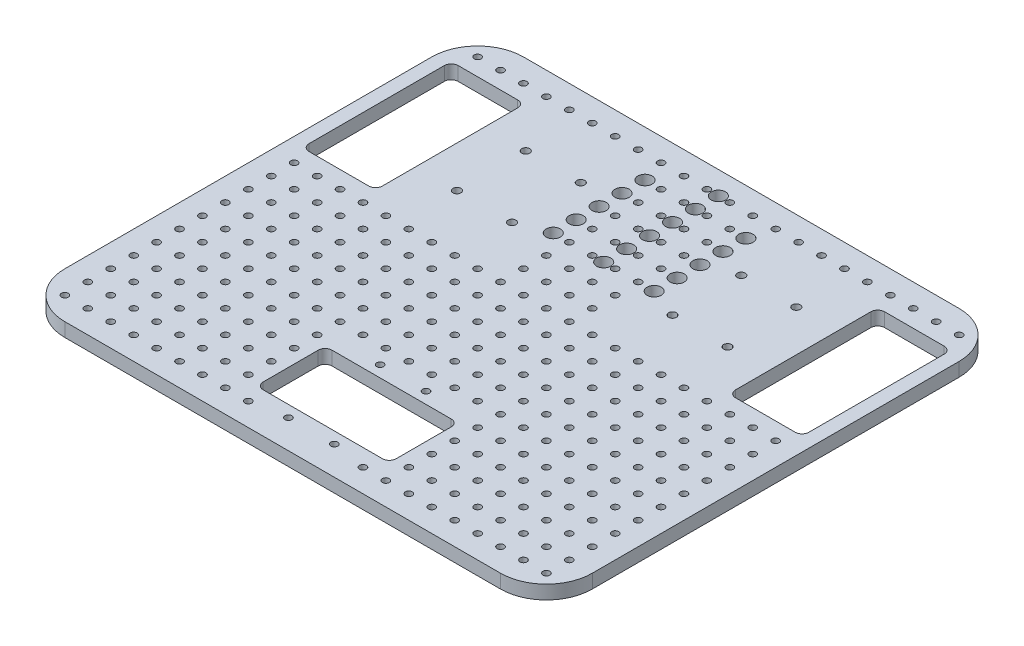
SolidWorks part; units mm, degrees
ref_plane "Спереди" through (0, 0, 0) normal (0, 0, 1) x (1, 0, 0)
ref_plane "Сверху" through (0, 0, 0) normal (0, 1, 0) x (1, 0, 0)
ref_plane "Справа" through (0, 0, 0) normal (1, 0, 0) x (0, 0, -1)
sketch "Эскиз1" plane through (0, 0, 0) normal (0, 1, 0) x (1, 0, 0)
  line L0 (94.4, 150) -> (0, 150) construction
  line L1 (0, 0) -> (230, 0)
  line L6 (115, 0) -> (115, 118.2603) construction
  line L10 (230, 0) -> (230, 200)
  line L28 (230, 200) -> (0, 200)
  line L29 (0, 200) -> (0, 0)
  circle A16 centre (80, 135) radius 1.73
  circle A19 centre (80, 165) radius 1.73
  circle A22 centre (56, 165) radius 1.73
  circle A23 centre (56, 135) radius 1.73
  circle A24 centre (150, 135) radius 1.73
  circle A25 centre (174, 135) radius 1.73
  circle A26 centre (150, 165) radius 1.73
  circle A27 centre (174, 165) radius 1.73
  point P7 (115, 25)
  dimension "D1" = 230
  dimension "D2" = 200
  dimension "D3" = 150
  dimension "D7" = 24
  dimension "D8" = 30
  dimension "D9" = 35
extrude "Бобышка-Вытянуть1" add sketch "Эскиз1" along normal blind 6
fillet "Скругление1" radius 20 4 edges at (0, 3, 0) (230, 3, 0) (230, 3, -200) (0, 3, -200)
sketch "Эскиз2" plane through (0, 6, 0) normal (0, 1, 0) x (1, 0, 0)
  line L0 (174, 165) -> (174, 135) construction
  line L1 (224, 182.5) -> (192, 182.5)
  line L2 (224, 182.5) -> (224, 117.5)
  line L3 (224, 117.5) -> (192, 117.5)
  line L4 (192, 182.5) -> (192, 117.5)
  line L5 (174, 150) -> (192, 150) construction
  line L6 (115, 200) -> (115, 0) construction
  line L7 (210, 200) -> (20, 200) construction
  line L8 (20, 0) -> (210, 0) construction
  line L9 (56, 150) -> (38, 150) construction
  line L10 (56, 165) -> (56, 135) construction
  line L11 (38, 182.5) -> (38, 117.5)
  line L12 (6, 117.5) -> (38, 117.5)
  line L13 (6, 182.5) -> (6, 117.5)
  line L14 (6, 182.5) -> (38, 182.5)
  line L15 (86, 32.5) -> (144, 32.5) construction
  line L16 (86, 47.5) -> (144, 47.5)
  line L17 (86, 47.5) -> (86, 17.5)
  line L18 (86, 17.5) -> (144, 17.5)
  line L19 (144, 47.5) -> (144, 17.5)
  circle A0 centre (105, 12.5) radius 1.5
  circle A1 centre (125, 12.5) radius 1.5
  circle A2 centre (105, 52.5) radius 1.5
  circle A3 centre (125, 52.5) radius 1.5
  dimension "D7" = 3
  dimension "D1" = 65
  dimension "D2" = 18
  dimension "D3" = 32
  dimension "D4" = 58
  dimension "D5" = 30
  dimension "D6" = 17.5
  dimension "D8" = 20
  dimension "D9" = 40
extrude "Вырез-Вытянуть1" cut sketch "Эскиз2" against normal blind 10
fillet "Скругление2" radius 3 12 edges at (224, 3, -117.5) (224, 3, -182.5) (192, 3, -182.5) (192, 3, -117.5) (6, 3, -117.5) (38, 3, -117.5) (38, 3, -182.5) (6, 3, -182.5) (86, 3, -17.5) (144, 3, -17.5) (144, 3, -47.5) (86, 3, -47.5)
sketch "Эскиз3" plane through (0, 6, 0) normal (0, 1, 0) x (1, 0, 0)
  line L0 (20, 0) -> (210, 0) construction
  line L1 (0, 180) -> (0, 20) construction
  line L2 (115, 190) -> (115, 200) construction
  line L3 (210, 200) -> (20, 200) construction
  circle A0 centre (10, 10) radius 1.5
  circle A1 centre (20, 10) radius 1.5
  circle A2 centre (30, 10) radius 1.5
  circle A3 centre (40, 10) radius 1.5
  circle A4 centre (50, 10) radius 1.5
  circle A5 centre (60, 10) radius 1.5
  circle A6 centre (70, 10) radius 1.5
  circle A7 centre (80, 10) radius 1.5
  circle A8 centre (90, 10) radius 1.5
  circle A13 centre (140, 10) radius 1.5
  circle A14 centre (150, 10) radius 1.5
  circle A15 centre (160, 10) radius 1.5
  circle A16 centre (170, 10) radius 1.5
  circle A17 centre (180, 10) radius 1.5
  circle A18 centre (190, 10) radius 1.5
  circle A19 centre (200, 10) radius 1.5
  circle A20 centre (210, 10) radius 1.5
  circle A21 centre (220, 10) radius 1.5
  circle A22 centre (20, 20) radius 1.5
  circle A23 centre (30, 20) radius 1.5
  circle A24 centre (40, 20) radius 1.5
  circle A25 centre (50, 20) radius 1.5
  circle A26 centre (60, 20) radius 1.5
  circle A27 centre (70, 20) radius 1.5
  circle A28 centre (80, 20) radius 1.5
  circle A35 centre (150, 20) radius 1.5
  circle A36 centre (160, 20) radius 1.5
  circle A37 centre (170, 20) radius 1.5
  circle A38 centre (180, 20) radius 1.5
  circle A39 centre (190, 20) radius 1.5
  circle A40 centre (200, 20) radius 1.5
  circle A41 centre (210, 20) radius 1.5
  circle A42 centre (220, 20) radius 1.5
  circle A43 centre (20, 30) radius 1.5
  circle A44 centre (30, 30) radius 1.5
  circle A45 centre (40, 30) radius 1.5
  circle A46 centre (50, 30) radius 1.5
  circle A47 centre (60, 30) radius 1.5
  circle A48 centre (70, 30) radius 1.5
  circle A49 centre (80, 30) radius 1.5
  circle A56 centre (150, 30) radius 1.5
  circle A57 centre (160, 30) radius 1.5
  circle A58 centre (170, 30) radius 1.5
  circle A59 centre (180, 30) radius 1.5
  circle A60 centre (190, 30) radius 1.5
  circle A61 centre (200, 30) radius 1.5
  circle A62 centre (210, 30) radius 1.5
  circle A63 centre (220, 30) radius 1.5
  circle A64 centre (20, 40) radius 1.5
  circle A65 centre (30, 40) radius 1.5
  circle A66 centre (40, 40) radius 1.5
  circle A67 centre (50, 40) radius 1.5
  circle A68 centre (60, 40) radius 1.5
  circle A69 centre (70, 40) radius 1.5
  circle A70 centre (80, 40) radius 1.5
  circle A77 centre (150, 40) radius 1.5
  circle A78 centre (160, 40) radius 1.5
  circle A79 centre (170, 40) radius 1.5
  circle A80 centre (180, 40) radius 1.5
  circle A81 centre (190, 40) radius 1.5
  circle A82 centre (200, 40) radius 1.5
  circle A83 centre (210, 40) radius 1.5
  circle A84 centre (220, 40) radius 1.5
  circle A85 centre (20, 50) radius 1.5
  circle A86 centre (30, 50) radius 1.5
  circle A87 centre (40, 50) radius 1.5
  circle A88 centre (50, 50) radius 1.5
  circle A89 centre (60, 50) radius 1.5
  circle A90 centre (70, 50) radius 1.5
  circle A91 centre (80, 50) radius 1.5
  circle A98 centre (150, 50) radius 1.5
  circle A99 centre (160, 50) radius 1.5
  circle A100 centre (170, 50) radius 1.5
  circle A101 centre (180, 50) radius 1.5
  circle A102 centre (190, 50) radius 1.5
  circle A103 centre (200, 50) radius 1.5
  circle A104 centre (210, 50) radius 1.5
  circle A105 centre (220, 50) radius 1.5
  circle A106 centre (20, 60) radius 1.5
  circle A107 centre (30, 60) radius 1.5
  circle A108 centre (40, 60) radius 1.5
  circle A109 centre (50, 60) radius 1.5
  circle A110 centre (60, 60) radius 1.5
  circle A111 centre (70, 60) radius 1.5
  circle A112 centre (80, 60) radius 1.5
  circle A113 centre (90, 60) radius 1.5
  circle A114 centre (100, 60) radius 1.5
  circle A115 centre (110, 60) radius 1.5
  circle A116 centre (120, 60) radius 1.5
  circle A117 centre (130, 60) radius 1.5
  circle A118 centre (140, 60) radius 1.5
  circle A119 centre (150, 60) radius 1.5
  circle A120 centre (160, 60) radius 1.5
  circle A121 centre (170, 60) radius 1.5
  circle A122 centre (180, 60) radius 1.5
  circle A123 centre (190, 60) radius 1.5
  circle A124 centre (200, 60) radius 1.5
  circle A125 centre (210, 60) radius 1.5
  circle A126 centre (220, 60) radius 1.5
  circle A127 centre (20, 70) radius 1.5
  circle A128 centre (30, 70) radius 1.5
  circle A129 centre (40, 70) radius 1.5
  circle A130 centre (50, 70) radius 1.5
  circle A131 centre (60, 70) radius 1.5
  circle A132 centre (70, 70) radius 1.5
  circle A133 centre (80, 70) radius 1.5
  circle A134 centre (90, 70) radius 1.5
  circle A135 centre (100, 70) radius 1.5
  circle A136 centre (110, 70) radius 1.5
  circle A137 centre (120, 70) radius 1.5
  circle A138 centre (130, 70) radius 1.5
  circle A139 centre (140, 70) radius 1.5
  circle A140 centre (150, 70) radius 1.5
  circle A141 centre (160, 70) radius 1.5
  circle A142 centre (170, 70) radius 1.5
  circle A143 centre (180, 70) radius 1.5
  circle A144 centre (190, 70) radius 1.5
  circle A145 centre (200, 70) radius 1.5
  circle A146 centre (210, 70) radius 1.5
  circle A147 centre (220, 70) radius 1.5
  circle A148 centre (20, 80) radius 1.5
  circle A149 centre (30, 80) radius 1.5
  circle A150 centre (40, 80) radius 1.5
  circle A151 centre (50, 80) radius 1.5
  circle A152 centre (60, 80) radius 1.5
  circle A153 centre (70, 80) radius 1.5
  circle A154 centre (80, 80) radius 1.5
  circle A155 centre (90, 80) radius 1.5
  circle A156 centre (100, 80) radius 1.5
  circle A157 centre (110, 80) radius 1.5
  circle A158 centre (120, 80) radius 1.5
  circle A159 centre (130, 80) radius 1.5
  circle A160 centre (140, 80) radius 1.5
  circle A161 centre (150, 80) radius 1.5
  circle A162 centre (160, 80) radius 1.5
  circle A163 centre (170, 80) radius 1.5
  circle A164 centre (180, 80) radius 1.5
  circle A165 centre (190, 80) radius 1.5
  circle A166 centre (200, 80) radius 1.5
  circle A167 centre (210, 80) radius 1.5
  circle A168 centre (220, 80) radius 1.5
  circle A169 centre (20, 90) radius 1.5
  circle A170 centre (30, 90) radius 1.5
  circle A171 centre (40, 90) radius 1.5
  circle A172 centre (50, 90) radius 1.5
  circle A173 centre (60, 90) radius 1.5
  circle A174 centre (70, 90) radius 1.5
  circle A175 centre (80, 90) radius 1.5
  circle A176 centre (90, 90) radius 1.5
  circle A177 centre (100, 90) radius 1.5
  circle A178 centre (110, 90) radius 1.5
  circle A179 centre (120, 90) radius 1.5
  circle A180 centre (130, 90) radius 1.5
  circle A181 centre (140, 90) radius 1.5
  circle A182 centre (150, 90) radius 1.5
  circle A183 centre (160, 90) radius 1.5
  circle A184 centre (170, 90) radius 1.5
  circle A185 centre (180, 90) radius 1.5
  circle A186 centre (190, 90) radius 1.5
  circle A187 centre (200, 90) radius 1.5
  circle A188 centre (210, 90) radius 1.5
  circle A189 centre (220, 90) radius 1.5
  circle A190 centre (20, 100) radius 1.5
  circle A191 centre (30, 100) radius 1.5
  circle A192 centre (40, 100) radius 1.5
  circle A193 centre (50, 100) radius 1.5
  circle A194 centre (60, 100) radius 1.5
  circle A195 centre (70, 100) radius 1.5
  circle A196 centre (80, 100) radius 1.5
  circle A197 centre (90, 100) radius 1.5
  circle A198 centre (100, 100) radius 1.5
  circle A199 centre (110, 100) radius 1.5
  circle A200 centre (120, 100) radius 1.5
  circle A201 centre (130, 100) radius 1.5
  circle A202 centre (140, 100) radius 1.5
  circle A203 centre (150, 100) radius 1.5
  circle A204 centre (160, 100) radius 1.5
  circle A205 centre (170, 100) radius 1.5
  circle A206 centre (180, 100) radius 1.5
  circle A207 centre (190, 100) radius 1.5
  circle A208 centre (200, 100) radius 1.5
  circle A209 centre (210, 100) radius 1.5
  circle A210 centre (220, 100) radius 1.5
  circle A211 centre (20, 110) radius 1.5
  circle A212 centre (30, 110) radius 1.5
  circle A213 centre (40, 110) radius 1.5
  circle A214 centre (50, 110) radius 1.5
  circle A215 centre (60, 110) radius 1.5
  circle A216 centre (70, 110) radius 1.5
  circle A217 centre (80, 110) radius 1.5
  circle A218 centre (90, 110) radius 1.5
  circle A219 centre (100, 110) radius 1.5
  circle A220 centre (110, 110) radius 1.5
  circle A221 centre (120, 110) radius 1.5
  circle A222 centre (130, 110) radius 1.5
  circle A223 centre (140, 110) radius 1.5
  circle A224 centre (150, 110) radius 1.5
  circle A225 centre (160, 110) radius 1.5
  circle A226 centre (170, 110) radius 1.5
  circle A227 centre (180, 110) radius 1.5
  circle A228 centre (190, 110) radius 1.5
  circle A229 centre (200, 110) radius 1.5
  circle A230 centre (210, 110) radius 1.5
  circle A231 centre (220, 110) radius 1.5
  circle A240 centre (100, 120) radius 1.5
  circle A241 centre (110, 120) radius 1.5
  circle A242 centre (120, 120) radius 1.5
  circle A243 centre (130, 120) radius 1.5
  circle A261 centre (100, 130) radius 1.5
  circle A262 centre (110, 130) radius 1.5
  circle A263 centre (120, 130) radius 1.5
  circle A264 centre (130, 130) radius 1.5
  circle A282 centre (100, 140) radius 1.5
  circle A283 centre (110, 140) radius 1.5
  circle A284 centre (120, 140) radius 1.5
  circle A285 centre (130, 140) radius 1.5
  circle A303 centre (100, 150) radius 1.5
  circle A304 centre (110, 150) radius 1.5
  circle A305 centre (120, 150) radius 1.5
  circle A306 centre (130, 150) radius 1.5
  circle A324 centre (100, 160) radius 1.5
  circle A325 centre (110, 160) radius 1.5
  circle A326 centre (120, 160) radius 1.5
  circle A327 centre (130, 160) radius 1.5
  circle A345 centre (100, 170) radius 1.5
  circle A346 centre (110, 170) radius 1.5
  circle A347 centre (120, 170) radius 1.5
  circle A348 centre (130, 170) radius 1.5
  circle A366 centre (100, 180) radius 1.5
  circle A367 centre (110, 180) radius 1.5
  circle A368 centre (120, 180) radius 1.5
  circle A369 centre (130, 180) radius 1.5
  circle A379 centre (20, 190) radius 1.5
  circle A380 centre (30, 190) radius 1.5
  circle A381 centre (40, 190) radius 1.5
  circle A382 centre (50, 190) radius 1.5
  circle A383 centre (60, 190) radius 1.5
  circle A384 centre (70, 190) radius 1.5
  circle A385 centre (80, 190) radius 1.5
  circle A386 centre (90, 190) radius 1.5
  circle A387 centre (100, 190) radius 1.5
  circle A388 centre (110, 190) radius 1.5
  circle A389 centre (120, 190) radius 1.5
  circle A390 centre (130, 190) radius 1.5
  circle A391 centre (140, 190) radius 1.5
  circle A392 centre (150, 190) radius 1.5
  circle A393 centre (160, 190) radius 1.5
  circle A394 centre (170, 190) radius 1.5
  circle A395 centre (180, 190) radius 1.5
  circle A396 centre (190, 190) radius 1.5
  circle A397 centre (200, 190) radius 1.5
  circle A398 centre (210, 190) radius 1.5
  circle A399 centre (220, 190) radius 1.5
  circle A400 centre (10, 20) radius 1.5
  circle A401 centre (10, 30) radius 1.5
  circle A402 centre (10, 40) radius 1.5
  circle A403 centre (10, 50) radius 1.5
  circle A404 centre (10, 60) radius 1.5
  circle A405 centre (10, 70) radius 1.5
  circle A406 centre (10, 80) radius 1.5
  circle A407 centre (10, 90) radius 1.5
  circle A408 centre (10, 100) radius 1.5
  circle A409 centre (10, 110) radius 1.5
  circle A417 centre (10, 190) radius 1.5
  circle A418 centre (20, 120) radius 1.5 [skipped]
  circle A419 centre (30, 120) radius 1.5 [skipped]
  circle A420 centre (40, 120) radius 1.5 [skipped]
  circle A421 centre (50, 120) radius 1.5 [skipped]
  circle A422 centre (60, 120) radius 1.5 [skipped]
  circle A423 centre (70, 120) radius 1.5 [skipped]
  circle A424 centre (80, 120) radius 1.5 [skipped]
  circle A425 centre (90, 120) radius 1.5 [skipped]
  circle A426 centre (20, 130) radius 1.5 [skipped]
  circle A427 centre (30, 130) radius 1.5 [skipped]
  circle A428 centre (40, 130) radius 1.5 [skipped]
  circle A429 centre (50, 130) radius 1.5 [skipped]
  circle A430 centre (60, 130) radius 1.5 [skipped]
  circle A431 centre (70, 130) radius 1.5 [skipped]
  circle A432 centre (80, 130) radius 1.5 [skipped]
  circle A433 centre (90, 130) radius 1.5 [skipped]
  circle A434 centre (20, 140) radius 1.5 [skipped]
  circle A435 centre (30, 140) radius 1.5 [skipped]
  circle A436 centre (40, 140) radius 1.5 [skipped]
  circle A437 centre (50, 140) radius 1.5 [skipped]
  circle A438 centre (60, 140) radius 1.5 [skipped]
  circle A439 centre (70, 140) radius 1.5 [skipped]
  circle A440 centre (80, 140) radius 1.5 [skipped]
  circle A441 centre (90, 140) radius 1.5 [skipped]
  circle A442 centre (20, 150) radius 1.5 [skipped]
  circle A443 centre (30, 150) radius 1.5 [skipped]
  circle A444 centre (40, 150) radius 1.5 [skipped]
  circle A445 centre (50, 150) radius 1.5 [skipped]
  circle A446 centre (60, 150) radius 1.5 [skipped]
  circle A447 centre (70, 150) radius 1.5 [skipped]
  circle A448 centre (80, 150) radius 1.5 [skipped]
  circle A449 centre (90, 150) radius 1.5 [skipped]
  circle A450 centre (20, 160) radius 1.5 [skipped]
  circle A451 centre (30, 160) radius 1.5 [skipped]
  circle A452 centre (40, 160) radius 1.5 [skipped]
  circle A453 centre (50, 160) radius 1.5 [skipped]
  circle A454 centre (60, 160) radius 1.5 [skipped]
  circle A455 centre (70, 160) radius 1.5 [skipped]
  circle A456 centre (80, 160) radius 1.5 [skipped]
  circle A457 centre (90, 160) radius 1.5 [skipped]
  circle A458 centre (20, 170) radius 1.5 [skipped]
  circle A459 centre (30, 170) radius 1.5 [skipped]
  circle A460 centre (40, 170) radius 1.5 [skipped]
  circle A461 centre (50, 170) radius 1.5 [skipped]
  circle A462 centre (60, 170) radius 1.5 [skipped]
  circle A463 centre (70, 170) radius 1.5 [skipped]
  circle A464 centre (80, 170) radius 1.5 [skipped]
  circle A465 centre (90, 170) radius 1.5 [skipped]
  circle A466 centre (20, 180) radius 1.5 [skipped]
  circle A467 centre (30, 180) radius 1.5 [skipped]
  circle A468 centre (40, 180) radius 1.5 [skipped]
  circle A469 centre (50, 180) radius 1.5 [skipped]
  circle A470 centre (60, 180) radius 1.5 [skipped]
  circle A471 centre (70, 180) radius 1.5 [skipped]
  circle A472 centre (80, 180) radius 1.5 [skipped]
  circle A473 centre (90, 180) radius 1.5 [skipped]
  circle A474 centre (10, 120) radius 1.5 [skipped]
  circle A475 centre (10, 130) radius 1.5 [skipped]
  circle A476 centre (10, 140) radius 1.5 [skipped]
  circle A477 centre (10, 150) radius 1.5 [skipped]
  circle A478 centre (10, 160) radius 1.5 [skipped]
  circle A479 centre (10, 170) radius 1.5 [skipped]
  circle A480 centre (10, 180) radius 1.5 [skipped]
  circle A481 centre (140, 120) radius 1.5 [skipped]
  circle A482 centre (150, 120) radius 1.5 [skipped]
  circle A483 centre (160, 120) radius 1.5 [skipped]
  circle A484 centre (170, 120) radius 1.5 [skipped]
  circle A485 centre (180, 120) radius 1.5 [skipped]
  circle A486 centre (190, 120) radius 1.5 [skipped]
  circle A487 centre (200, 120) radius 1.5 [skipped]
  circle A488 centre (210, 120) radius 1.5 [skipped]
  circle A489 centre (220, 120) radius 1.5 [skipped]
  circle A490 centre (140, 130) radius 1.5 [skipped]
  circle A491 centre (150, 130) radius 1.5 [skipped]
  circle A492 centre (160, 130) radius 1.5 [skipped]
  circle A493 centre (170, 130) radius 1.5 [skipped]
  circle A494 centre (180, 130) radius 1.5 [skipped]
  circle A495 centre (190, 130) radius 1.5 [skipped]
  circle A496 centre (200, 130) radius 1.5 [skipped]
  circle A497 centre (210, 130) radius 1.5 [skipped]
  circle A498 centre (220, 130) radius 1.5 [skipped]
  circle A499 centre (140, 140) radius 1.5 [skipped]
  circle A500 centre (150, 140) radius 1.5 [skipped]
  circle A501 centre (160, 140) radius 1.5 [skipped]
  circle A502 centre (170, 140) radius 1.5 [skipped]
  circle A503 centre (180, 140) radius 1.5 [skipped]
  circle A504 centre (190, 140) radius 1.5 [skipped]
  circle A505 centre (200, 140) radius 1.5 [skipped]
  circle A506 centre (210, 140) radius 1.5 [skipped]
  circle A507 centre (220, 140) radius 1.5 [skipped]
  circle A508 centre (140, 150) radius 1.5 [skipped]
  circle A509 centre (150, 150) radius 1.5 [skipped]
  circle A510 centre (160, 150) radius 1.5 [skipped]
  circle A511 centre (170, 150) radius 1.5 [skipped]
  circle A512 centre (180, 150) radius 1.5 [skipped]
  circle A513 centre (190, 150) radius 1.5 [skipped]
  circle A514 centre (200, 150) radius 1.5 [skipped]
  circle A515 centre (210, 150) radius 1.5 [skipped]
  circle A516 centre (220, 150) radius 1.5 [skipped]
  circle A517 centre (140, 160) radius 1.5 [skipped]
  circle A518 centre (150, 160) radius 1.5 [skipped]
  circle A519 centre (160, 160) radius 1.5 [skipped]
  circle A520 centre (170, 160) radius 1.5 [skipped]
  circle A521 centre (180, 160) radius 1.5 [skipped]
  circle A522 centre (190, 160) radius 1.5 [skipped]
  circle A523 centre (200, 160) radius 1.5 [skipped]
  circle A524 centre (210, 160) radius 1.5 [skipped]
  circle A525 centre (220, 160) radius 1.5 [skipped]
  circle A526 centre (140, 170) radius 1.5 [skipped]
  circle A527 centre (150, 170) radius 1.5 [skipped]
  circle A528 centre (160, 170) radius 1.5 [skipped]
  circle A529 centre (170, 170) radius 1.5 [skipped]
  circle A530 centre (180, 170) radius 1.5 [skipped]
  circle A531 centre (190, 170) radius 1.5 [skipped]
  circle A532 centre (200, 170) radius 1.5 [skipped]
  circle A533 centre (210, 170) radius 1.5 [skipped]
  circle A534 centre (220, 170) radius 1.5 [skipped]
  circle A535 centre (140, 180) radius 1.5 [skipped]
  circle A536 centre (150, 180) radius 1.5 [skipped]
  circle A537 centre (160, 180) radius 1.5 [skipped]
  circle A538 centre (170, 180) radius 1.5 [skipped]
  circle A539 centre (180, 180) radius 1.5 [skipped]
  circle A540 centre (190, 180) radius 1.5 [skipped]
  circle A541 centre (200, 180) radius 1.5 [skipped]
  circle A542 centre (210, 180) radius 1.5 [skipped]
  circle A543 centre (220, 180) radius 1.5 [skipped]
  circle A544 centre (90, 20) radius 1.5 [skipped]
  circle A545 centre (100, 20) radius 1.5 [skipped]
  circle A546 centre (110, 20) radius 1.5 [skipped]
  circle A547 centre (120, 20) radius 1.5 [skipped]
  circle A548 centre (130, 20) radius 1.5 [skipped]
  circle A549 centre (140, 20) radius 1.5 [skipped]
  circle A550 centre (90, 30) radius 1.5 [skipped]
  circle A551 centre (100, 30) radius 1.5 [skipped]
  circle A552 centre (110, 30) radius 1.5 [skipped]
  circle A553 centre (120, 30) radius 1.5 [skipped]
  circle A554 centre (130, 30) radius 1.5 [skipped]
  circle A555 centre (140, 30) radius 1.5 [skipped]
  circle A556 centre (90, 40) radius 1.5 [skipped]
  circle A557 centre (100, 40) radius 1.5 [skipped]
  circle A558 centre (110, 40) radius 1.5 [skipped]
  circle A559 centre (120, 40) radius 1.5 [skipped]
  circle A560 centre (130, 40) radius 1.5 [skipped]
  circle A561 centre (140, 40) radius 1.5 [skipped]
  circle A562 centre (90, 50) radius 1.5 [skipped]
  circle A563 centre (100, 50) radius 1.5 [skipped]
  circle A564 centre (110, 50) radius 1.5 [skipped]
  circle A565 centre (120, 50) radius 1.5 [skipped]
  circle A566 centre (130, 50) radius 1.5 [skipped]
  circle A567 centre (140, 50) radius 1.5 [skipped]
  circle A568 centre (100, 10) radius 1.5 [skipped]
  circle A569 centre (110, 10) radius 1.5 [skipped]
  circle A570 centre (120, 10) radius 1.5 [skipped]
  circle A571 centre (130, 10) radius 1.5 [skipped]
  circle A572 centre (115, 190) radius 3.1
  circle A573 centre (115, 180) radius 3.1
  circle A574 centre (115, 170) radius 3.1
  circle A575 centre (115, 160) radius 3.1
  circle A576 centre (115, 150) radius 3.1
  circle A577 centre (115, 140) radius 3.1
  circle A578 centre (137, 180) radius 3.1
  circle A579 centre (93, 180) radius 3.1
  circle A580 centre (93, 170) radius 3.1
  circle A581 centre (137, 170) radius 3.1
  circle A582 centre (93, 160) radius 3.1
  circle A583 centre (137, 160) radius 3.1
  circle A584 centre (93, 150) radius 3.1
  circle A585 centre (137, 150) radius 3.1
  circle A586 centre (93, 140) radius 3.1
  circle A587 centre (137, 140) radius 3.1
  dimension "D1" = 3
  dimension "D5" = 6.2
  dimension "D2" = 10
  dimension "D3" = 10
  dimension "D6" = 10
  dimension "D4" = 19
  dimension "D7" = 6
  dimension "D8" = 2
  dimension "D9" = 2
  dimension "D10" = 5
extrude "Вырез-Вытянуть2" cut sketch "Эскиз3" against normal blind 10
